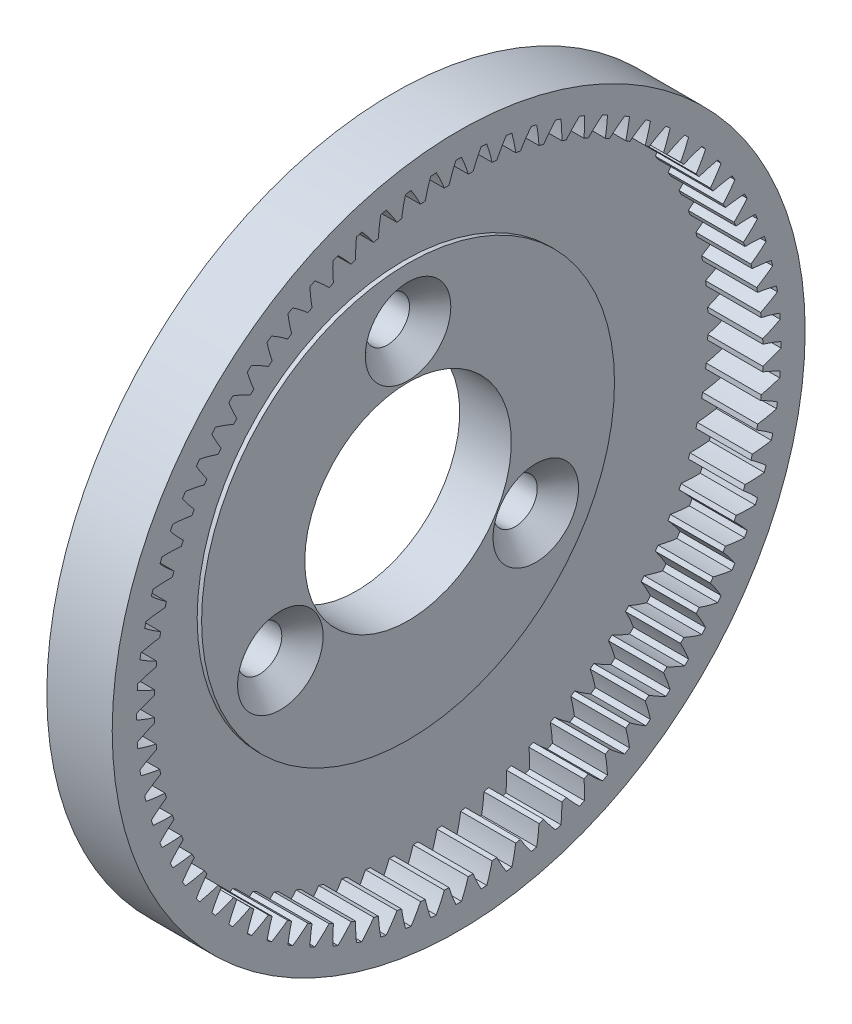
SolidWorks part; units mm, degrees
ref_plane "Plane1" through (0, 0, 0) normal (0, 0, 1) x (1, 0, 0)
ref_plane "Plane2" through (0, 0, 0) normal (0, 1, 0) x (1, 0, 0)
ref_plane "Plane3" through (0, 0, 0) normal (1, 0, 0) x (0, 0, -1)
sketch "HoldingSke" plane through (0, 0, 0) normal (0, 1, 0) x (1, 0, 0)
  line L0 (0, 0) -> (211.7119, -1200.6776)
  line L1 (-15, 0) -> (100, 0) construction
  line L2 (0, 0) -> (-2.1039, 2.3779)
  line L3 (0, 0) -> (-11.863, 4.5341)
  line L4 (0, 0) -> (1.4996, 8.5048)
  line L5 (0, 0) -> (-23.7986, -8.8762)
  line L6 (0, 0) -> (-10.5278, -7.1032)
  line L7 (-2.1039, 2.3779) -> (3.3635, 27.1825)
  line L8 (-76.2, 54.61) -> (-54.61, 54.61)
  line L9 (-71.009, 38.7566) -> (-53.1078, 45.2721)
  line L10 (-76.2, 71.12) -> (104.1128, 71.12)
  line L11 (0, 0) -> (-3.7338, 0)
  line L12 (-76.2, 101.6) -> (-76.1787, 101.6)
  line L13 (24.9733, 27.94) -> (52.9518, 28.4284)
  line L14 (24.9733, 27.94) -> (25.0241, 27.9398)
  line L15 (24.9733, 27.94) -> (100.4021, 29.52)
  circle A0 centre (0, 0) radius 23.495
  circle A1 centre (0, 0) radius 12.7
  circle A2 centre (0, 0) radius 12.7
  dimension "MHD" = 25.4
  dimension "Hub_dia" = 25.4
  dimension "Diameter" = 46.99
  dimension "Num_teeth" = 80
  dimension "Pitch_radius" = 180.3128
  dimension "Pitch" = 1219.2
  dimension "Width" = 3.7338
  dimension "Overall_len" = 25.4
  dimension "Show_teeth" = 80
  dimension "Thickness" = 12.7
  dimension "OAL" = 25.4001
  dimension "T_dim" = 21.59
  dimension "Ap" = 20
  dimension "H" = 19.05
  dimension "Backlash" = 0.0213
  dimension "Addendum_fac" = 1
  dimension "Dedendum_fac" = 1.2
  dimension "Clearance_fac" = 0.2
  dimension "Dedendum_add" = 0.0508
sketch "BasProSke" plane through (0, 0, 0) normal (0, 1, 0) x (1, 0, 0)
  line L0 (-10, 0) -> (60, 0) construction
  line L1 (0, 20.6375) -> (0, 23.495)
  line L2 (0, 20.6375) -> (3.7338, 20.6375)
  line L3 (3.7338, 20.6375) -> (3.7338, 23.495)
  line L4 (3.7338, 23.495) -> (0, 23.495)
  dimension "Diameter" = 46.99
  dimension "Thickness" = 3.7338
  dimension "Inside_diameter" = 41.275
revolve "Base-Revolve" add sketch "BasProSke" angle 360 about L0
sketch "TooCutSke" plane through (0, 0, 0) normal (1, 0, 0) x (0, 0, -1)
  line L3 (0.4689, 21.1615) -> (0.4689, 53.6633) construction
  line L4 (0, 0) -> (0, 59.563) construction
  line L5 (0, 0) -> (-2.6825, 68.2748) construction
  line L6 (-9.4765, 17.5426) -> (37.1108, 19.373) construction
  circle A0 centre (0, 0) radius 21.1667 construction
  circle A1 centre (0, 0) radius 21.8525 construction
  circle A2 centre (0, 0) radius 17.9011 construction
  circle A3 centre (0, 0) radius 20.6121 construction
  arc A4 (0.6551, 20.6017) -> (0.1899, 21.8516) centre (-9.4765, 17.5426) ccw
  arc A5 (0.6551, 20.6017) -> (-0.6551, 20.6017) centre (0, 0) ccw
  arc A6 (0.1899, 21.8516) -> (-0.1899, 21.8516) centre (0, 0) ccw
  arc A7 (-0.1899, 21.8516) -> (-0.6551, 20.6017) centre (9.4765, 17.5426) ccw
  dimension "Pitch_dia" = 42.3333
  dimension "Base_dia" = 35.8023
  dimension "Root_dia" = 43.7049
  dimension "Overcut_dia" = 41.2242
  dimension "Flank_rad" = 10.5833
  dimension "Half_ang" = 2.25
  dimension "Half_CT" = 0.4689
extrude "ToothCut" cut sketch "TooCutSke" along normal through all
fillet "Breaks" [suppressed] radius 0.0529
fillet "RootFillets" [suppressed] radius 0.1566
pattern_circular "TeethCuts" count 80 every 4.5 about axis through (-10, 0, 0) along (1, 0, 0) of "RootFillets", "Breaks", "ToothCut"
sketch "Esboço1" plane through (0, 0, 0) normal (-1, 0, 0) x (0, 0, 1)
  circle A0 centre (0, 0) radius 23.495 construction
  circle A1 centre (0, 0) radius 23.495
extrude "Ressalto-extrusão1" add sketch "Esboço1" along normal blind 3.2
sketch "Esboço2" plane through (-3.2, 0, 0) normal (-1, 0, 0) x (0, 0, 1)
  line L0 (0, 0) -> (0, 10) construction
  line L1 (0, 0) -> (-8.6603, -5) construction
  line L2 (0, 0) -> (8.6603, -5) construction
  circle A0 centre (0, 0) radius 7.005
  circle A1 centre (0, 10) radius 1.5
  circle A2 centre (-8.6603, -5) radius 1.5
  circle A3 centre (8.6603, -5) radius 1.5
  dimension "D1" = 3
  dimension "D2" = 14.01
  dimension "D3" = 120
  dimension "D4" = 120
  dimension "D5" = 10
extrude "Corte-extrusão1" cut sketch "Esboço2" against normal up to next
chamfer "Chanfro1" distance 2.5 angle 60 1 edges at (-3.2, 0, 23.495) first distance on face at (3.7338, 0, 23.495)
sketch "Esboço3" plane through (0, 0, 0) normal (1, 0, 0) x (0, 0, -1)
  circle A0 centre (0, 0) radius 7.005 construction
  circle A1 centre (-8.6603, -5) radius 1.5 construction
  circle A2 centre (8.6603, -5) radius 1.5 construction
  circle A3 centre (0, 10) radius 1.5 construction
  circle A4 centre (0, 0) radius 7.005
  circle A5 centre (-8.6603, -5) radius 1.5
  circle A6 centre (8.6603, -5) radius 1.5
  circle A7 centre (0, 10) radius 1.5
  circle A8 centre (0, 0) radius 14
  dimension "D1" = 28
extrude "Ressalto-extrusão2" add sketch "Esboço3" along normal blind 0.3
chamfer "Chanfro2" distance 1.4 angle 45 3 edges at (0.3, -5, -10.1603) (0.3, -5, 7.1603) (0.3, 10, -1.5)
equation "' \"Pitch@HoldingSke\" = 4"
equation "' \"Num_teeth@HoldingSke\" = 24"
equation "' \"Ap@HoldingSke\" =  14.5"
equation "' \"Width@HoldingSke\" = 0.5"
equation "' \"Diameter@HoldingSke\" = 8"
equation "' \"Show_teeth@HoldingSke\" = 100"
equation "' \"Backlash@HoldingSke\" = 0.009"
equation "' \"Addendum_fac@HoldingSke\" = 1.0"
equation "' \"Dedendum_fac@HoldingSke\" = 1.25"
equation "' \"Dedendum_add@HoldingSke\" = 0.00005"
equation "' \"Clearance_fac@HoldingSke\" = 0.25"
equation "\"Overcut_dia@TooCutSke\" = (\"Num_teeth@HoldingSke\" - 2 * \"Addendum_fac@HoldingSke\") / \"Pitch@HoldingSke\" - 0.002"
equation "\"Pitch_dia@TooCutSke\" = \"Num_teeth@HoldingSke\" / \"Pitch@HoldingSke\""
equation "\"Base_dia@TooCutSke\" = \"Num_teeth@HoldingSke\" / \"Pitch@HoldingSke\" * cos((\"Ap@HoldingSke\"  * 3.14159265 / 180)) * 0.90"
equation "\"Root_dia@TooCutSke\" = \"Num_teeth@HoldingSke\"  / \"Pitch@HoldingSke\" + 2 *  \"Dedendum_fac@HoldingSke\"/ \"Pitch@HoldingSke\" + \"Dedendum_add@HoldingSke\" * 2"
equation "\"Half_ang@TooCutSke\" = 180 / \"Num_teeth@HoldingSke\""
equation "\"Half_CT@TooCutSke\" = \"Num_teeth@HoldingSke\" / \"Pitch@HoldingSke\" * sin((3.14159265 / 2 / \"Num_teeth@HoldingSke\")) / 2 + 10 * \"Backlash@HoldingSke\" / 4"
equation "\"Flank_rad@TooCutSke\" = \"Num_teeth@HoldingSke\" / \"Pitch@HoldingSke\" / 4"
equation "\"Radius@RootFillets\"= \"Clearance_fac@HoldingSke\" / \"Pitch@HoldingSke\" + \"Dedendum_add@HoldingSke\""
equation "\"Break_rad@Breaks\" = 0.02 / \"Pitch@HoldingSke\" * 5"
equation "\"Num_teeth@TeethCuts\" = int( \"Show_teeth@HoldingSke\" ) + 1"
equation "\"Num_teeth@TeethCuts\" = ((sgn( \"Num_teeth@TeethCuts\" - \"Num_teeth@HoldingSke\" )-1)*( \"Num_teeth@TeethCuts\" - \"Num_teeth@HoldingSke\" ))/-2+ \"Num_teeth@HoldingSke\""
equation "\"Num_teeth@TeethCuts\" = ((sgn( \"Num_teeth@TeethCuts\" - 2.0)+1)*( \"Num_teeth@TeethCuts\" - 2.0))/2 +2.0"
equation "\"Angle@TeethCuts\" = 360.0 / \"Num_teeth@HoldingSke\""
equation "\"Diameter@BasProSke\" = \"Num_teeth@HoldingSke\"  / \"Pitch@HoldingSke\" + 2 *  \"Dedendum_fac@HoldingSke\"/ \"Pitch@HoldingSke\" + \"Dedendum_add@HoldingSke\" * 2 + 0.002"
equation "\"Diameter@BasProSke\" = ((sgn( \"Diameter@BasProSke\"  - \"Diameter@HoldingSke\" )+1)*( \"Diameter@BasProSke\"  - \"Diameter@HoldingSke\" ))/2 + \"Diameter@HoldingSke\""
equation "\"Inside_diameter@BasProSke\" =  (\"Num_teeth@HoldingSke\" - 2 * \"Addendum_fac@HoldingSke\") / \"Pitch@HoldingSke\" "
equation "\"Thickness@BasProSke\"  = \"Width@HoldingSke\""
